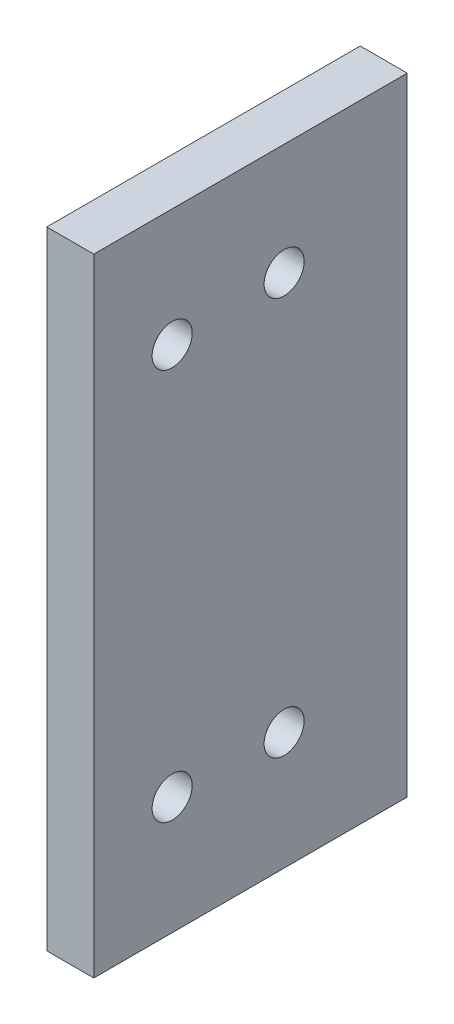
SolidWorks part; units mm, degrees
ref_plane "Front Plane" through (0, 0, 0) normal (1, 0, 0) x (0, 1, 0)
ref_plane "Top Plane" through (0, 0, 0) normal (0, 0, 1) x (0, 1, 0)
ref_plane "Right Plane" through (0, 0, 0) normal (0, 1, 0) x (-1, 0, 0)
sketch "Sketch1" plane through (0, 0, 0) normal (1, 0, 0) x (0, 1, 0)
  line L6 (-40, -4.29) -> (40, -4.29) construction
  line L7 (-40, -20) -> (40, -20)
  line L8 (-40, -20) -> (-40, 20)
  line L9 (-40, 20) -> (40, 20)
  line L10 (40, -20) -> (40, 20)
  line L11 (-40, -20) -> (40, 20) construction
  line L12 (-40, 20) -> (40, -20) construction
  circle A1 centre (-25, -4.29) radius 2.555
  circle A2 centre (25.8, -4.29) radius 2.555
  circle A4 centre (-25, 10) radius 2.555
  circle A6 centre (25, 10) radius 2.555
  point P0 (0, 0)
  point P2 (0, 0)
  point P15 (0, 0)
  dimension "D5" = 15
  dimension "D6" = 5.11
  dimension "D7" = 5.11
  dimension "D8" = 10
  dimension "D9" = 5.11
  dimension "D10" = 15
  dimension "D13" = 5.11
  dimension "D1" = 80
  dimension "D2" = 40
  dimension "D3" = 15.71
  dimension "D4" = 50.8
  dimension "D11" = 10
  dimension "D14" = 15
extrude "Boss-Extrude2" add sketch "Sketch1" along normal blind 6 contours L7 L10 L9 L8
extrude "Cut-Extrude3" cut sketch "Sketch1<3>" along normal up to next contours A2 | A1 | A4 | A6
sketch "Sketch1<3>" plane through (0, 0, 0) normal (1, 0, 0) x (0, 1, 0) same geometry as "Sketch1"
